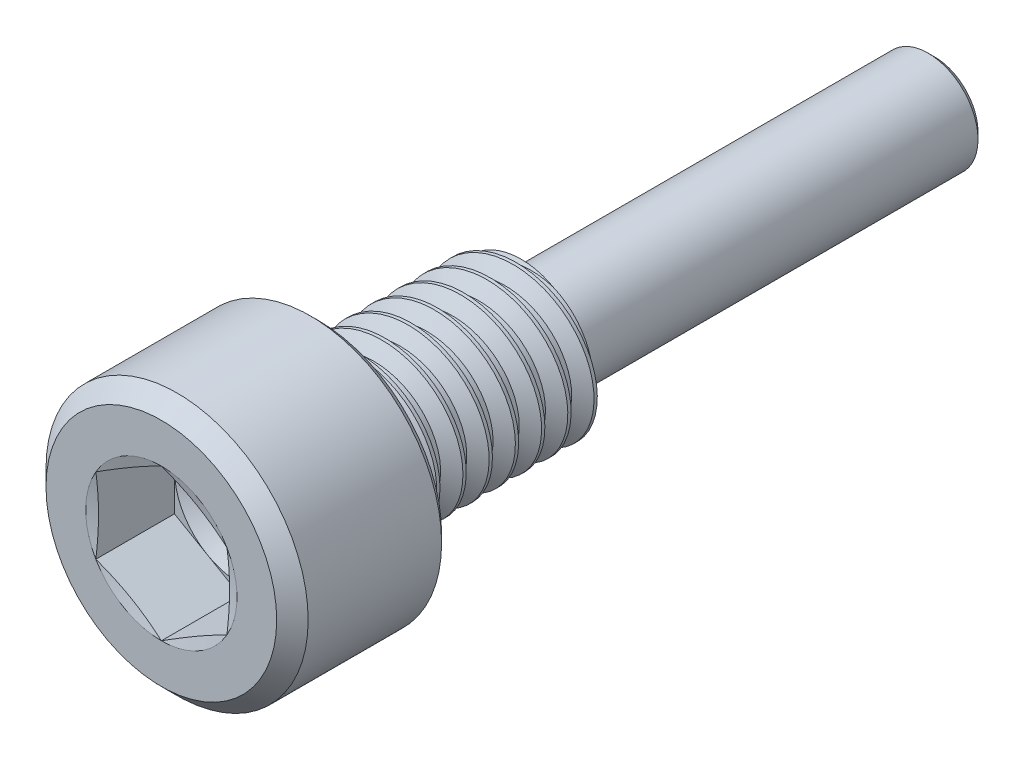
SolidWorks part; units mm, degrees
ref_plane "Front Plane" through (0, 0, 0) normal (0, 0, 1) x (1, 0, 0)
ref_plane "Top Plane" through (0, 0, 0) normal (0, 1, 0) x (1, 0, 0)
ref_plane "Right Plane" through (0, 0, 0) normal (1, 0, 0) x (0, 0, -1)
sketch "Sketch1" plane through (0, 0, 0) normal (1, 0, 0) x (0, 0, -1)
  line L0 (0, 0) -> (12.9407, 0) construction
  line L1 (0, 0) -> (0, 4.4)
  line L2 (0, 4.4) -> (0.6, 5)
  line L3 (0.6, 5) -> (5.69, 5)
  line L4 (6, 4.69) -> (6, 3.4)
  line L5 (6.68, 3) -> (30.5, 3)
  line L6 (30.5, 3) -> (31, 2.5)
  line L7 (31, 2.5) -> (31, 0)
  line L8 (31, 0) -> (0, 0)
  line L9 (5.69, 5) -> (6, 4.69)
  line L11 (6, 3.4) -> (6, 3)
  line L12 (6, 3) -> (6.68, 3)
  point P6 (6, 5)
  dimension "D1" = 45
  dimension "DK" = 10
  dimension "D3" = 45
  dimension "length" = 25
  dimension "K" = 6
  dimension "V" = 0.6
  dimension "HOLESIZE" = 6
  dimension "D4" = 5
  dimension "D5" = 45
  dimension "DW" = 9.38
  dimension "F" = 0.68
  dimension "DA" = 6.8
revolve "Revolve1" add sketch "Sketch1" angle 360 about L0
cosmetic thread "Cosmetic Thread1" [suppressed] parameters "D1"=22, "D2"=6
sketch "Sketch2" plane through (0, 0, 0) normal (0, 0, 1) x (1, 0, 0)
  line L0 (0, 0) -> (0, 2.8868) construction
  line L2 (0, 2.8868) -> (-2.5, 1.4434)
  line L3 (-2.5, 1.4434) -> (-2.5, -1.4434)
  line L4 (-2.5, -1.4434) -> (0, -2.8868)
  line L5 (0, -2.8868) -> (2.5, -1.4434)
  line L6 (2.5, -1.4434) -> (2.5, 1.4434)
  line L7 (2.5, 1.4434) -> (0, 2.8868)
  circle A0 centre (0, 0) radius 2.5 construction
  dimension "S" = 5
extrude "Cut-Extrude1" cut sketch "Sketch2" against normal blind 3
sketch "Sketch3" plane through (0, 0, 0) normal (1, 0, 0) x (0, 0, -1)
  line L0 (3, 0) -> (31, 0) construction
  line L1 (31, -2.5) -> (31, 2.5) construction
  line L2 (3, 0) -> (3, 2.5)
  line L4 (3, 2.5) -> (4.4434, 0)
  line L5 (4.4434, 0) -> (3, 0)
  line L6 (0, 4.4) -> (0, -4.4) construction
  dimension "DRILLANG" = 60
  dimension "DRILL DEPTH" = 3
  dimension "S2" = 5
revolve "Cut-Revolve2" cut sketch "Sketch3" angle 360 about L0
sketch "Sketch4" plane through (0, 0, 0) normal (1, 0, 0) x (0, 0, -1)
  line L0 (0, 0) -> (4.6121, 0) construction
  line L1 (0, 2.8868) -> (0, 2.5)
  line L2 (0, 4.4) -> (0, -4.4) construction
  line L3 (0, 2.5) -> (0.1036, 2.5)
  line L4 (0.1036, 2.5) -> (0, 2.8868)
  point P12 (0.0518, 2.5)
  dimension "D1" = 5
  dimension "D2" = 15
revolve "Cut-Revolve3" cut sketch "Sketch4" angle 360 about L0
thread "Filetage3" pitch 1 method cut trim with start face yes trim with end face yes profile "Profil de filetage1" start angle 0, offset 2, length 0, pitch 1, diameter 6
ref_plane "Plan1" through (3, 0, -32.5) normal (0, -1, 0) x (1, 0, 0)
sketch "Profil de filetage1" plane through (3, 0, -32.5) normal (0, -1, 0) x (1, 0, 0)
  line L0 (0, 0) -> (0, 1) construction
  line L11 (0, 0) -> (0, 0.875)
  line L12 (0, 0.875) -> (-0.5413, 0.5625)
  line L13 (-0.5413, 0.5625) -> (-0.5413, 0.3125)
  line L15 (-0.5413, 0.3125) -> (0, 0)
  line L17 (-0.5413, 0.4375) -> (0, 0.4375) construction
  point P2 (0, 0)
  dimension "Pitch" = 1
  dimension "Profile_Angle" = 60
  dimension "Profile_Land" = 0.25
  dimension "Profile_Height" = 0.5413
sketch "Esquisse8" plane through (0, 0, -31) normal (0, 0, -1) x (-1, 0, 0)
  circle A0 centre (0, 0) radius 4.2456
extrude "Enlèv. mat.-Extru.2" cut sketch "Esquisse8" against normal offset from surface (1.5 mm away) 23.5 up to face at (4.69, 0, -6)
sketch "Esquisse4" plane through (0, 0, -29.5) normal (0, 0, -1) x (-1, 0, 0)
  circle A0 centre (0, 0) radius 1.9
  dimension "D1" = 3.8
extrude "Enlèv. mat.-Extru.1" cut sketch "Esquisse4" against normal offset from surface (15.5 mm away) 8 flip side to cut up to face at (4.69, 0, -6)
hole_wizard "Dégagement M1.61" positions "Esquisse5" profile "Esquisse7" hole size "M1.6" standard "Ansi Metric"
sketch "Esquisse5" plane through (0, 0, -29.5) normal (0, 0, -1) x (-1, 0, 0)
  point P0 (0, 0)
sketch "Esquisse7" plane through (0, 0, -29.5) normal (1, 0, 0) x (0, 1, 0)
  line L0 (0, 0) -> (0, 0.6408)
  line L1 (0, 0.6408) -> (0.9, 0.1)
  line L2 (0.9, 0.1) -> (0.9, 0)
  line L5 (0.9, 0) -> (0, 0)
  line L10 (0, 0.6408) -> (-0.9, 0.1) construction
  line L11 (0, -6.35) -> (0, 107.95) construction
  dimension "Diamètre du perçage" = 1.8
  dimension "Profondeur du perçage" = 0.1
  dimension "Angle de pointe" = 118
chamfer "Chanfrein1" distance 0.25 angle 45 1 edges at (-1.9, 0, -29.5)
